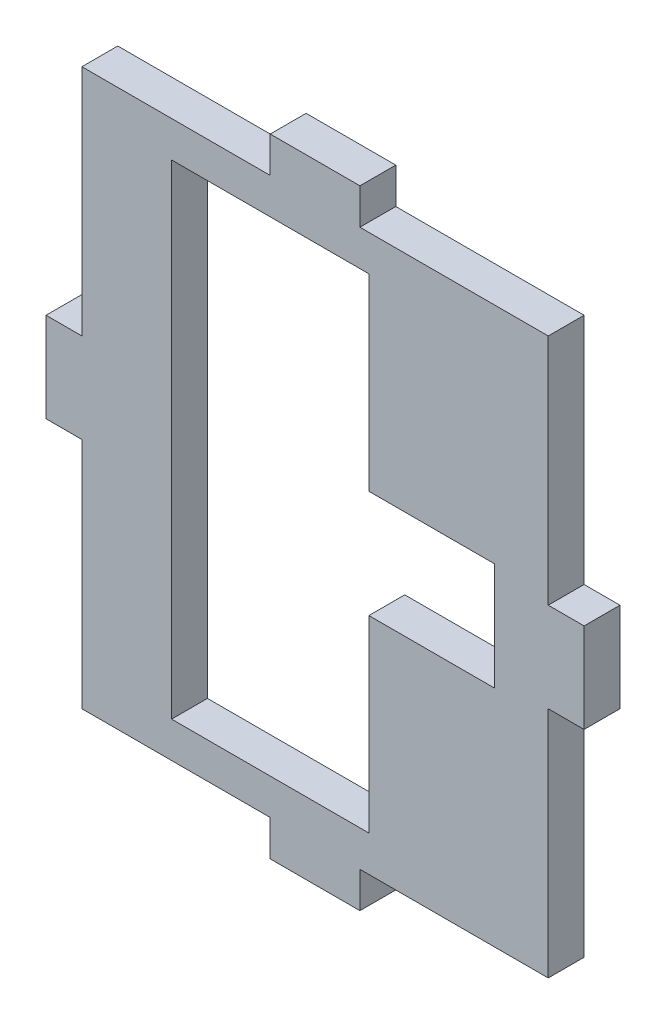
SolidWorks part; units mm, degrees
ref_plane "Front Plane" through (0, 0, 0) normal (0, 0, 1) x (1, 0, 0)
ref_plane "Top Plane" through (0, 0, 0) normal (0, 1, 0) x (1, 0, 0)
ref_plane "Right Plane" through (0, 0, 0) normal (1, 0, 0) x (0, 0, -1)
sketch "Sketch1" plane through (0, 0, 0) normal (0, 0, 1) x (1, 0, 0)
  line L1 (0, 0) -> (52, 0)
  line L2 (0, 0) -> (0, 62)
  line L3 (0, 62) -> (52, 62)
  line L4 (52, 0) -> (52, 62)
  dimension "D1" = 52
  dimension "D2" = 62
extrude "Boss-Extrude1" add sketch "Sketch1" along normal blind 4
sketch "Sketch2" plane through (0, 0, 4) normal (0, 0, 1) x (1, 0, 0)
  line L0 (0, 62) -> (0, 0) construction
  line L1 (0, 36) -> (-4, 36)
  line L2 (0, 36) -> (0, 26)
  line L3 (0, 26) -> (-4, 26)
  line L4 (-4, 36) -> (-4, 26)
  line L5 (52, 0) -> (52, 62) construction
  line L6 (52, 36) -> (56, 36)
  line L7 (52, 36) -> (52, 26)
  line L8 (52, 26) -> (56, 26)
  line L9 (56, 36) -> (56, 26)
  line L10 (0, 0) -> (52, 0) construction
  line L11 (21, 0) -> (31, 0)
  line L12 (21, 0) -> (21, -4)
  line L13 (21, -4) -> (31, -4)
  line L14 (31, 0) -> (31, -4)
  line L15 (52, 62) -> (0, 62) construction
  line L16 (21, 62) -> (31, 62)
  line L17 (21, 62) -> (21, 66)
  line L18 (21, 66) -> (31, 66)
  line L19 (31, 62) -> (31, 66)
  line L21 (26, 0) -> (26, 23.7889) construction
  dimension "D1" = 10
  dimension "D2" = 10
  dimension "D3" = 26
  dimension "D4" = 10
  dimension "D6" = 4
extrude "Boss-Extrude2" add sketch "Sketch2" against normal blind 4
sketch "Sketch3" plane through (0, 0, 4) normal (0, 0, 1) x (1, 0, 0)
  line L0 (52, 0) -> (52, 26) construction
  line L1 (10, 58) -> (32, 58)
  line L2 (10, 58) -> (10, 4)
  line L3 (10, 4) -> (32, 4)
  line L4 (32, 58) -> (32, 4)
  line L5 (0, 26) -> (0, 0) construction
  line L6 (21, 62) -> (0, 62) construction
  line L7 (0, 0) -> (21, 0) construction
  dimension "D1" = 20
  dimension "D2" = 10
  dimension "D3" = 4
  dimension "D4" = 4
extrude "Cut-Extrude1" cut sketch "Sketch3" against normal blind 10
sketch "Sketch4" plane through (0, 0, 4) normal (0, 0, 1) x (1, 0, 0)
  line L0 (32, 31) -> (47.7948, 31) construction
  line L1 (32, 4) -> (32, 58) construction
  line L3 (27.8061, 25) -> (46, 25)
  line L4 (27.8061, 25) -> (27.8061, 37)
  line L5 (27.8061, 37) -> (46, 37)
  line L6 (46, 25) -> (46, 37)
  line L7 (27.8061, 25) -> (46, 37) construction
  line L8 (27.8061, 37) -> (46, 25) construction
  point P4 (36.903, 31)
  dimension "D1" = 12
  dimension "D2" = 14
extrude "Cut-Extrude2" cut sketch "Sketch4" against normal blind 10
